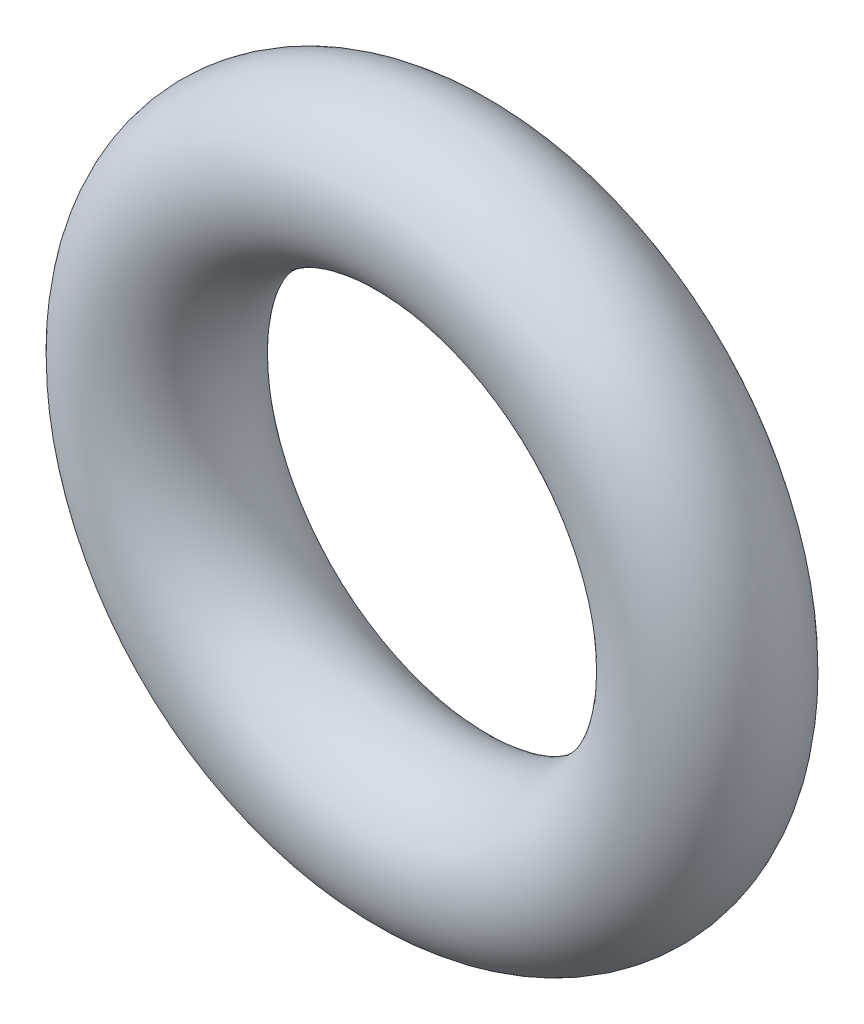
SolidWorks part; units mm, degrees
material "Rubber"
ref_plane "Front Plane" through (0, 0, 0) normal (0, 0, 1) x (1, 0, 0)
ref_plane "Top Plane" through (0, 0, 0) normal (0, 1, 0) x (1, 0, 0)
ref_plane "Right Plane" through (0, 0, 0) normal (1, 0, 0) x (0, 0, -1)
sketch "Sketch1" plane through (0, 0, 0) normal (1, 0, 0) x (0, 0, -1)
  line L0 (0, 0) -> (1.597, 0) construction
  circle A0 centre (0, 3.1242) radius 0.889
  dimension "D1" = 1.778
  dimension "D2" = 3.1242
revolve "Revolve1" add sketch "Sketch1" angle 360 about L0
sketch "Sketch2" plane through (0, 0, 0) normal (0, 0, 1) x (1, 0, 0)
  circle A0 centre (0, 0) radius 1.4478 construction
  dimension "D1" = 2.8956
equation "\"D2@Sketch1\"=0.176/2 + 0.07/2"
